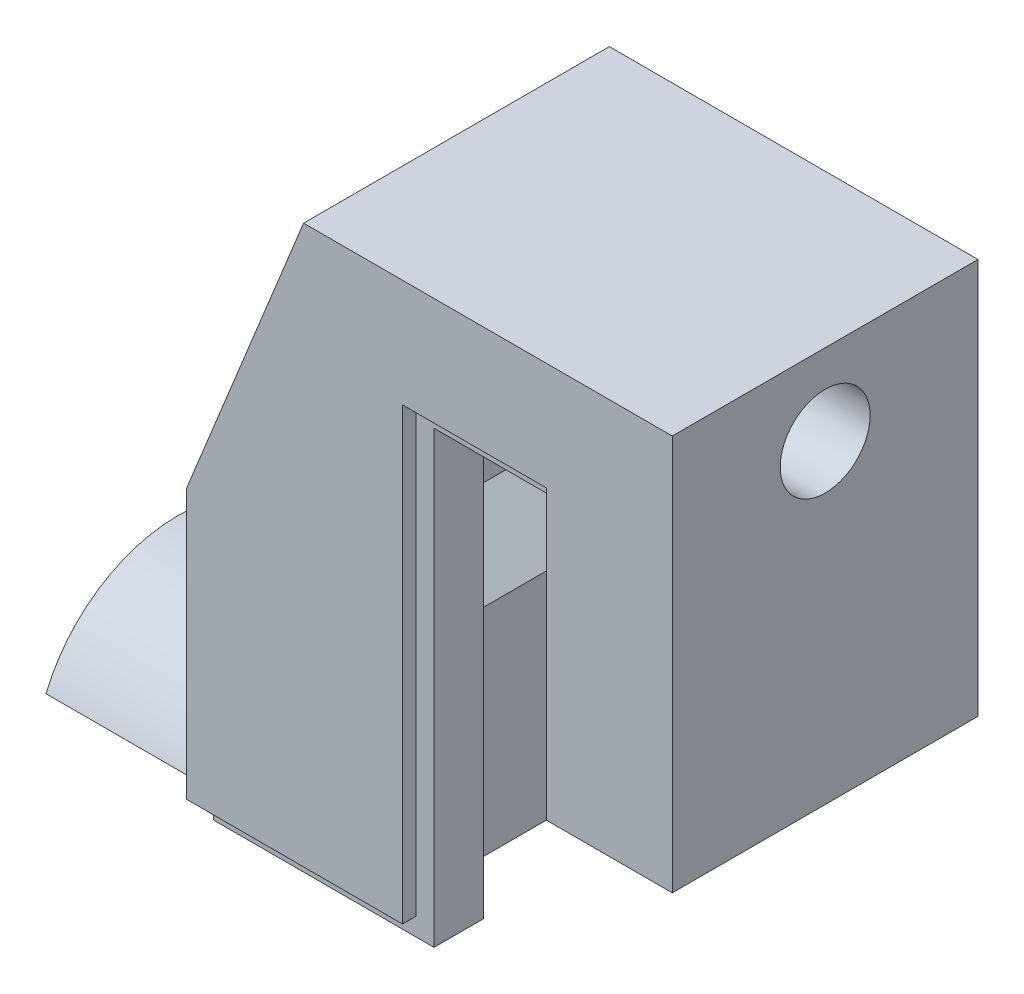
SolidWorks part; units mm, degrees
ref_plane "Front Plane" through (0, 0, 0) normal (0, 0, 1) x (1, 0, 0)
ref_plane "Top Plane" through (0, 0, 0) normal (0, 1, 0) x (1, 0, 0)
ref_plane "Right Plane" through (0, 0, 0) normal (1, 0, 0) x (0, 0, -1)
sketch "Sketch1" plane through (0, 0, 0) normal (0, 1, 0) x (1, 0, 0)
  line L1 (6.5, 8.5) -> (-6.5, 8.5)
  line L2 (6.5, 8.5) -> (6.5, -8.5)
  line L3 (6.5, -8.5) -> (-6.5, -8.5)
  line L4 (-6.5, 8.5) -> (-6.5, -8.5)
  line L5 (6.5, 8.5) -> (-6.5, -8.5) construction
  line L6 (6.5, -8.5) -> (-6.5, 8.5) construction
  point P0 (0, 0)
  dimension "D1" = 13
  dimension "D2" = 17
extrude "Boss-Extrude1" add sketch "Sketch1" along normal blind 30
sketch "Sketch2" plane through (-6.5, 0, 0) normal (-1, 0, 0) x (0, 0, 1)
  line L0 (-8.5, 0) -> (8.5, 0) construction
  line L1 (-8.5, -2) -> (8.5, -2) construction
  circle A1 centre (0, -2) radius 5.75
  dimension "D1" = 11.5
  dimension "D2" = 2
extrude "Cut-Extrude1" cut sketch "Sketch2" against normal blind 5
sketch "Sketch3" plane through (0, 0, 0) normal (0, -1, 0) x (1, 0, 0)
  line L0 (6.5, 8.5) -> (6.5, -8.5) construction
  line L1 (6.5, 5) -> (3.5, 5)
  line L2 (6.5, 5) -> (6.5, -5)
  line L3 (6.5, -5) -> (3.5, -5)
  line L4 (3.5, 5) -> (3.5, -5)
  line L6 (0, 0) -> (6.5, 0) construction
  dimension "D1" = 10
  dimension "D2" = 5
  dimension "D3" = 3
extrude "Cut-Extrude2" cut sketch "Sketch3" against normal through all
sketch "Sketch4" plane through (0, 30, 0) normal (0, 1, 0) x (1, 0, 0)
  line L1 (-6.5, 8.5) -> (20.5, 8.5)
  line L2 (-6.5, 8.5) -> (-6.5, -8.5)
  line L3 (-6.5, -8.5) -> (20.5, -8.5)
  line L4 (20.5, 8.5) -> (20.5, -8.5)
  dimension "D1" = 17
  dimension "D2" = 27
extrude "Boss-Extrude2" add sketch "Sketch4" along normal blind 2
sketch "Sketch5" plane through (0, 30, 0) normal (0, -1, 0) x (1, 0, 0)
  line L0 (20.5, -8.5) -> (6.5, -8.5) construction
  line L1 (20.5, 8.5) -> (13.5, 8.5)
  line L2 (20.5, 8.5) -> (20.5, -8.5)
  line L3 (20.5, -8.5) -> (13.5, -8.5)
  line L4 (13.5, 8.5) -> (13.5, -8.5)
  line L5 (6.5, 8.5) -> (6.5, 5) construction
  dimension "D1" = 7
extrude "Boss-Extrude3" add sketch "Sketch5" along normal blind 20
sketch "Sketch6" plane through (0, 30, 0) normal (0, -1, 0) x (1, 0, 0)
  line L1 (6.5, 5) -> (13.5, 5)
  line L2 (6.5, 5) -> (6.5, 8.5)
  line L3 (6.5, 8.5) -> (13.5, 8.5)
  line L4 (13.5, 5) -> (13.5, 8.5)
  line L5 (13.5, -8.5) -> (6.5, -8.5)
  line L6 (13.5, -8.5) -> (13.5, -5)
  line L7 (13.5, -5) -> (6.5, -5)
  line L8 (6.5, -8.5) -> (6.5, -5)
extrude "Boss-Extrude4" add sketch "Sketch6" along normal blind 5
sketch "Sketch7" plane through (20.5, 0, 0) normal (1, 0, 0) x (0, 0, -1)
  line L0 (-8.5, 32) -> (8.5, 32) construction
  circle A0 centre (0, 27.5) radius 2.5
  dimension "D1" = 5
  dimension "D2" = 4.5
extrude "Cut-Extrude3" cut sketch "Sketch7" against normal blind 7
sketch "Sketch9" plane through (0, 0, 8.5) normal (0, 0, 1) x (1, 0, 0)
  line L0 (0, 32) -> (-6.5, 16)
  line L1 (-6.5, 32) -> (20.5, 32) construction
  line L2 (-6.5, 32) -> (-6.5, 0) construction
  line L3 (-6.5, 16) -> (-6.5, 32)
  line L4 (-6.5, 32) -> (0, 32)
extrude "Cut-Extrude4" cut sketch "Sketch9" against normal through all
sketch "Sketch10" plane through (0, 0, 0) normal (0, -1, 0) x (1, 0, 0)
  line L0 (-5.75, 7.75) -> (-5.75, 5.391)
  line L1 (-6.5, 8.5) -> (6.5, 8.5)
  line L2 (6.5, 7.75) -> (-5.75, 7.75)
  line L3 (6.5, 8.5) -> (6.5, 5) construction
  line L4 (-1.5, 5.391) -> (-6.5, 5.391) construction
  line L8 (-6.5, -8.5) -> (6.5, -8.5)
  line L9 (6.5, -8.5) -> (6.5, -7.75)
  line L10 (6.5, -5) -> (6.5, -8.5) construction
  line L11 (6.5, -7.75) -> (-5.75, -7.75)
  line L15 (-5.75, 5.391) -> (-6.5, 5.391)
  line L16 (-6.5, 5.391) -> (-6.5, 8.5)
  line L17 (-5.75, -7.75) -> (-5.75, -5.391)
  line L18 (-6.5, -5.391) -> (-1.5, -5.391) construction
  line L19 (-5.75, -5.391) -> (-6.5, -5.391)
  line L20 (-6.5, -5.391) -> (-6.5, -8.5)
  line M11 (6.5, 5) -> (6.5, 8.5)
  line M12 (6.5, 8.5) -> (-6.5, 8.5)
  line M13 (-6.5, 8.5) -> (-6.5, 5.391)
  dimension "D1" = 0.75
  dimension "D2" = 0.75
  dimension "D3" = 0.75
  dimension "D4" = 0.75
extrude "Cut-Extrude5" cut sketch "Sketch10" against normal blind 1 contours L0 L2 M11 M12 M13 | L11 L17 L19 L20 L8 L9 region at (-0.9408, 0, 7.8862)
sketch "Sketch11" plane through (6.5, 0, 0) normal (1, 0, 0) x (0, 0, -1)
  line L0 (-8.5, 25) -> (-5, 25) construction
  line L1 (-8.5, 1) -> (-7.75, 1)
  line L2 (-8.5, 1) -> (-8.5, 25)
  line L3 (-8.5, 25) -> (-7.75, 25)
  line L4 (-7.75, 1) -> (-7.75, 25)
  line L10 (8.5, 1) -> (7.75, 1)
  line L11 (8.5, 1) -> (8.5, 25)
  line L12 (8.5, 25) -> (7.75, 25)
  line L13 (7.75, 1) -> (7.75, 25)
  dimension "D1" = 0.75
  dimension "D2" = 0.75
  dimension "D3" = 24
extrude "Cut-Extrude6" cut sketch "Sketch11" against normal blind 1
sketch "Sketch12" plane through (0, 25, 0) normal (0, -1, 0) x (1, 0, 0)
  line L0 (13.5, -8.5) -> (13.5, -5) construction
  line L1 (5.5, -8.5) -> (13.5, -8.5)
  line L2 (5.5, -8.5) -> (5.5, -7.75)
  line L3 (5.5, -7.75) -> (13.5, -7.75)
  line L4 (13.5, -8.5) -> (13.5, -7.75)
  line L6 (5.5, 7.75) -> (13.5, 7.75)
  line L7 (5.5, 7.75) -> (5.5, 8.5)
  line L8 (5.5, 8.5) -> (13.5, 8.5)
  line L9 (13.5, 7.75) -> (13.5, 8.5)
  dimension "D1" = 0.75
extrude "Cut-Extrude7" cut sketch "Sketch12" against normal blind 1
sketch "Sketch13" plane through (0, 10, 0) normal (0, -1, 0) x (1, 0, 0)
  line L0 (13.5, -8.5) -> (20.5, -8.5) construction
  line L2 (20.5, 8.5) -> (13.5, 8.5) construction
  line L4 (13.5, -8.5) -> (13.5, 8.5)
  line L6 (17, -8.5) -> (17, 8.5) construction
  spline S0 degree 3 poles (13.5, -8.5) (15.8571, -7.1465) (17.9872, 0.4151) (16.1685, 6.3162) (13.5, 8.5) knots 0 0 0 0 0.5 1 1 1 1
extrude "Cut-Extrude8" cut sketch "Sketch13" against normal blind 13 contours S0 L4
sketch "Sketch14" plane through (3.5, 0, 0) normal (1, 0, 0) x (0, 0, -1)
  line L0 (5, 30) -> (5, 0) construction
  line L1 (-5, 30) -> (5, 30)
  line L2 (-5, 30) -> (-5, 15)
  line L3 (-5, 15) -> (5, 15)
  line L4 (5, 30) -> (5, 15)
  dimension "D1" = 15
extrude "Cut-Extrude9" cut sketch "Sketch14" against normal blind 3
chamfer "Chamfer1" distance 3 angle 45 1 edges at (3.5, 15, 0)
sketch "Sketch15" plane through (-6.5, 0, 0) normal (-1, 0, 0) x (0, 0, 1)
  line L0 (-7.75, 0) -> (-5.391, 0) construction
  line L1 (-8.5, -2) -> (8.5, -2) construction
  line L3 (-7.75, 1) -> (-5.391, 1) construction
  line L4 (7.75, 1) -> (5.391, 1) construction
  line L5 (-6.3246, 1) -> (-7.3225, 1)
  line L6 (-5.391, 1) -> (-8.5, 1) construction
  line L7 (6.3246, 1) -> (7.3246, 1)
  line L8 (8.5, 1) -> (5.391, 1) construction
  arc A0 (-6.3246, 1) -> (6.3246, 1) centre (0, -2) cw
  arc A1 (-7.3225, 1) -> (7.3225, 1) centre (0, -2) cw
  line M7 (5.391, 1) -> (8.5, 1)
  line M11 (-8.5, 1) -> (-5.391, 1)
  dimension "D2" = 7
  dimension "D1" = 2
  dimension "D3" = 0.9979
  dimension "D4" = 1
extrude "Boss-Extrude5" add sketch "Sketch15" along normal blind 8 contours A1 A0 M11 M7 region at (-6.5, 1.1545, -6.8235)
sketch "Sketch16" plane through (-14.5, 0, 0) normal (-1, 0, 0) x (0, 0, 1)
  line L1 (8.5, 1) -> (7.3225, 1) construction
  line L2 (-7.3225, 1) -> (7.3225, 1)
  arc A1 (-7.3225, 1) -> (7.3225, 1) centre (0, -2) cw
extrude "Boss-Extrude6" add sketch "Sketch16" along normal blind 1
